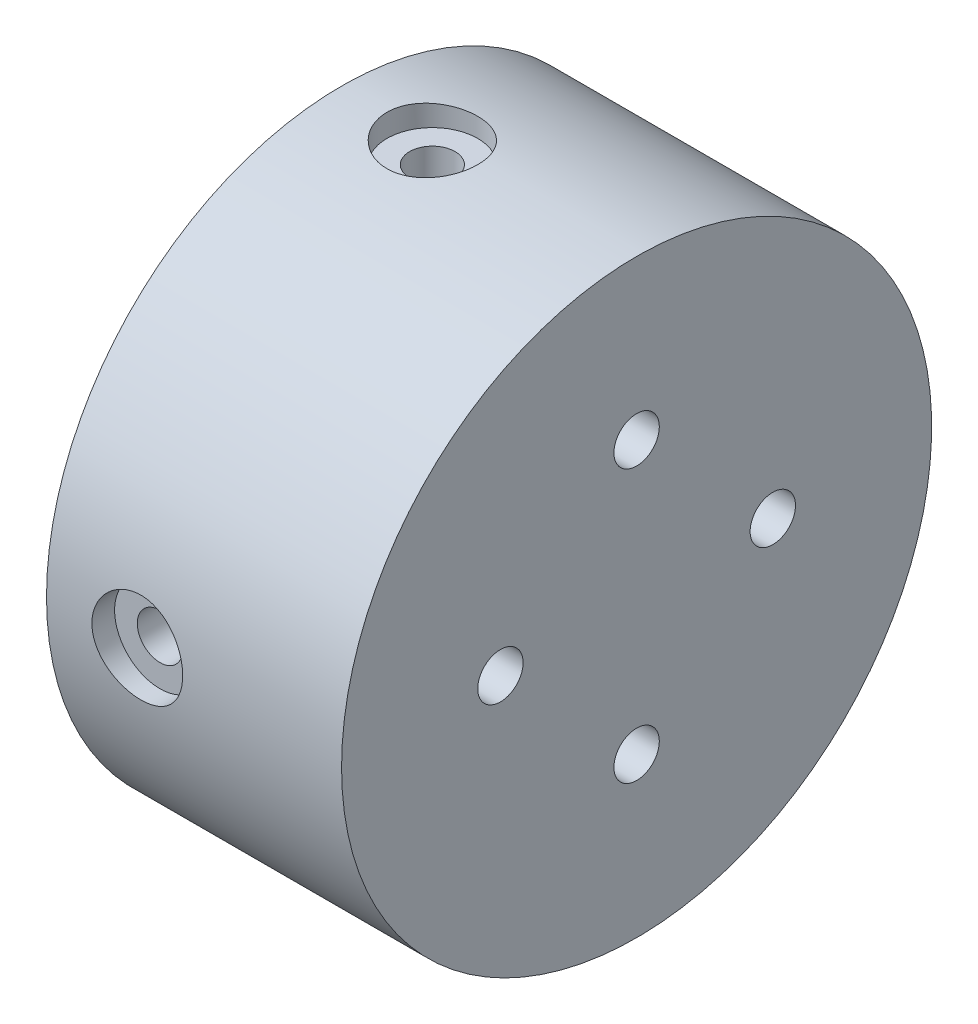
SolidWorks part; units mm, degrees
ref_plane "Спереди" through (0, 0, 0) normal (0, 0, 1) x (1, 0, 0)
ref_plane "Сверху" through (0, 0, 0) normal (0, 1, 0) x (1, 0, 0)
ref_plane "Справа" through (0, 0, 0) normal (1, 0, 0) x (0, 0, -1)
sketch "Эскиз1" plane through (0, 0, 0) normal (0, 0, 1) x (1, 0, 0)
  line L0 (0, 0) -> (67.9269, 0) construction
  line L1 (0, 13) -> (13, 13)
  line L2 (13, 13) -> (13, 0)
  line L6 (10, 0) -> (10, 10)
  line L7 (10, 10) -> (0, 10)
  line L8 (0, 10) -> (0, 13)
  line L9 (10, 0) -> (13, 0)
  dimension "D1" = 20
  dimension "D2" = 3
  dimension "D3" = 10
  dimension "D4" = 13
  dimension "D5" = 3
revolve "Повернуть1" add sketch "Эскиз1" angle 360 about L0
sketch "Эскиз2" plane through (13, 0, 0) normal (1, 0, 0) x (0, 0, -1)
  circle A0 centre (0, 6) radius 1
  dimension "D1" = 2
  dimension "D2" = 6
  dimension "D3" = 6
extrude "Вырез-Вытянуть1" cut sketch "Эскиз2" against normal up to next contours A0
ref_axis "Ось1" through (10, 0, 0) along (-1, 0, 0)
pattern_circular "Круговой массив1" count 4 over 360 about axis through (10, 0, 0) along (-1, 0, 0) of "Вырез-Вытянуть1"
ref_plane "Плоскость1" through (0, 0, 13) normal (0, 0, 1) x (1, 0, 0)
sketch "Эскиз5" plane through (0, 0, 13) normal (0, 0, 1) x (1, 0, 0)
  line L0 (0, 13) -> (0, -13) construction
  circle A0 centre (4, 0) radius 1
  dimension "D1" = 2
  dimension "D2" = 4
  dimension "D3" = 4
extrude "Вырез-Вытянуть2" cut sketch "Эскиз5" against normal blind 10 contours A0
pattern_circular "Круговой массив3" count 4 over 360 about axis through (10, 0, 0) along (-1, 0, 0) of "Вырез-Вытянуть2"
sketch "Эскиз7" plane through (0, 0, 13) normal (0, 0, 1) x (1, 0, 0)
  circle A0 centre (4, 0) radius 2
  dimension "D1" = 4
extrude "Вырез-Вытянуть3" cut sketch "Эскиз7" against normal blind 1 contours A0
pattern_circular "Круговой массив4" count 4 over 360 about axis through (10, 0, 0) along (-1, 0, 0) of "Вырез-Вытянуть3"
